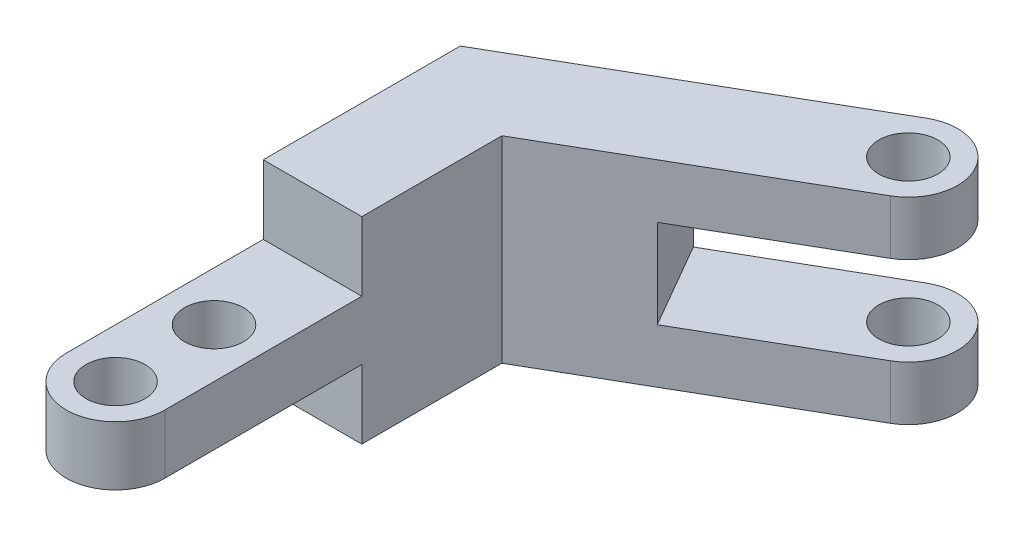
SolidWorks part; units mm, degrees
ref_plane "Front Plane" through (0, 0, 0) normal (0, 0, 1) x (1, 0, 0)
ref_plane "Top Plane" through (0, 0, 0) normal (0, 1, 0) x (1, 0, 0)
ref_plane "Right Plane" through (0, 0, 0) normal (1, 0, 0) x (0, 0, -1)
sketch "Sketch1" plane through (0, 0, 0) normal (0, 1, 0) x (1, 0, 0)
  line L6 (0, 0) -> (0, -20)
  line L11 (0, 0) -> (15, 8.6603)
  line L12 (5, -2.8868) -> (5, -20)
  line L13 (5, -2.8868) -> (17.5, 4.3301)
  line L14 (15, 8.6603) -> (17.5, 4.3301) construction
  line L15 (0, -20) -> (5, -20) construction
  circle A0 centre (16.25, 6.4952) radius 2.5
  circle A2 centre (2.5, -20) radius 2.5
  circle A3 centre (16.25, 6.4952) radius 1.5
  circle A4 centre (2.5, -20) radius 1.5
  circle A5 centre (2.5, -15) radius 1.5
  dimension "D5" = 3
  dimension "D6" = 3
  dimension "D1" = 20
  dimension "D2" = 120
  dimension "D3" = 15
  dimension "D4" = 5
  dimension "D7" = 2
extrude "Boss-Extrude1" add sketch "Sketch1" along normal blind 10 contours A2 L12 L13 A0 L11 L6 | A0 | A2 region at (7.6679, 0, -4.0393) region at (2.5, 0, 17.5707) region at (17.4646, 0, -8.599)
ref_plane "Plane1" through (0, 0, 0) normal (-0.5, 0, 0.866) x (0.866, 0, 0.5)
sketch "Sketch3" plane through (0, 0, 0) normal (-0.5, 0, -0.866) x (-0.866, 0, 0.5)
  line L0 (-8.6603, 10) -> (-8.6603, 0) construction
  line L1 (0, 10) -> (-17.3205, 10) construction
  line L2 (0, 0) -> (-17.3205, 0) construction
  line L3 (-17.3205, 5) -> (0, 5) construction
  line L4 (-17.3205, 10) -> (-17.3205, 0) construction
  line L6 (-25.9808, 2.75) -> (-8.6603, 2.75)
  line L7 (-25.9808, 2.75) -> (-25.9808, 7.25)
  line L8 (-25.9808, 7.25) -> (-8.6603, 7.25)
  line L9 (-8.6603, 2.75) -> (-8.6603, 7.25)
  line L10 (-25.9808, 2.75) -> (-8.6603, 7.25) construction
  line L11 (-25.9808, 7.25) -> (-8.6603, 2.75) construction
  dimension "D1" = 4.5
extrude "Cut-Extrude1" cut sketch "Sketch3" against normal up to surface (5 mm away) up to face at (11.25, 5, -0.7217)
sketch "Sketch5" plane through (0, 10, 0) normal (0, 1, 0) x (1, 0, 0)
  line L0 (0, -10) -> (5, -10) construction
  line L1 (0, 0) -> (0, -20) construction
  line L2 (5, -2.8868) -> (5, -20) construction
  line L4 (0, -10) -> (5, -10)
  line L5 (0, -10) -> (0, -23)
  line L6 (0, -23) -> (5, -23)
  line L7 (5, -10) -> (5, -23)
  dimension "D1" = 13
extrude "Cut-Extrude3" cut sketch "Sketch5" against normal blind 3.5
sketch "Sketch6" plane through (0, 0, 0) normal (0, -1, 0) x (1, 0, 0)
  line L0 (0, 10) -> (5, 10) construction
  line L1 (0, 0) -> (0, 20) construction
  line L3 (0, 10) -> (5, 10)
  line L4 (0, 10) -> (0, 23)
  line L5 (0, 23) -> (5, 23)
  line L6 (5, 10) -> (5, 23)
  dimension "D1" = 13
extrude "Cut-Extrude4" cut sketch "Sketch6" against normal blind 3.5
